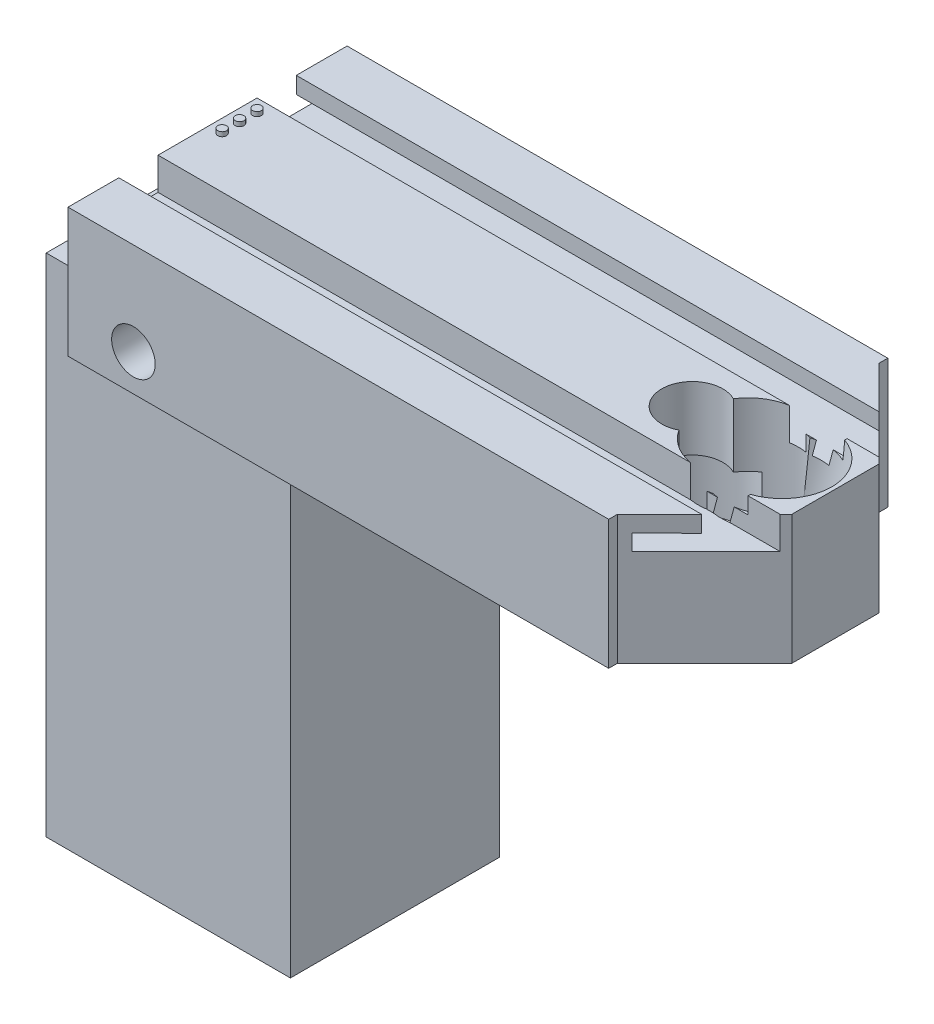
SolidWorks part; units mm, degrees
ref_plane "Front Plane" through (0, 0, 0) normal (0, 0, 1) x (1, 0, 0)
ref_plane "Top Plane" through (0, 0, 0) normal (0, 1, 0) x (1, 0, 0)
ref_plane "Right Plane" through (0, 0, 0) normal (1, 0, 0) x (0, 0, -1)
sketch "Sketch1" plane through (0, 0, 0) normal (0, 1, 0) x (1, 0, 0)
  line L0 (0, 15) -> (0, -15) construction
  line L1 (-23.5, -15) -> (23.5, -15)
  line L2 (-23.5, -15) -> (-23.5, 15)
  line L3 (-23.5, 15) -> (23.5, 15)
  line L4 (23.5, -15) -> (23.5, 15)
  line L5 (-23.5, -15) -> (23.5, 15) construction
  line L6 (-23.5, 15) -> (23.5, -15) construction
  point P0 (0, 0)
  dimension "D1" = 30
  dimension "D2" = 47
extrude "Boss-Extrude1" add sketch "Sketch1" along normal blind 14.8
sketch "Sketch2" plane through (0, 0, 0) normal (0, -1, 0) x (1, 0, 0)
  line L0 (16, 10) -> (16, -10) construction
  line L1 (7.75, 0) -> (20.75, 0) construction
  line L3 (23.5, 15) -> (23.5, -15) construction
  circle A0 centre (13.5, 0) radius 5.75
  point P13 (23.5, 0)
  dimension "D1" = 11.5
  dimension "D2" = 10
  dimension "D4" = 8.25
  dimension "D5" = 7.5
extrude "Cut-Extrude1" cut sketch "Sketch2" against normal through all
sketch "Sketch10" plane through (0, 0, 15) normal (0, 0, 1) x (1, 0, 0)
  line L1 (-23.5, 0) -> (-8.5, 0)
  line L2 (-23.5, 0) -> (-23.5, 23)
  line L3 (-23.5, 23) -> (-8.5, 23)
  line L4 (-8.5, 0) -> (-8.5, 23)
  line L6 (-23.5, 0) -> (23.5, 0) construction
  line L7 (-23.5, 14.8) -> (-23.5, 0) construction
  dimension "D1" = 23
  dimension "D2" = 15
  dimension "D3" = 0
extrude "Boss-Extrude2" add sketch "Sketch10" along normal blind 10
sketch "Sketch9" plane through (0, 0, 25) normal (0, 0, 1) x (1, 0, 0)
  line L0 (-8.5, 0) -> (-8.5, 14.8) construction
  line L2 (-20.445, 8.382) -> (-20.445, 0)
  line L3 (-20.445, 0) -> (-11.555, 0)
  line L4 (-11.555, 8.382) -> (-11.555, 0)
  line L5 (-11.555, 0) -> (-8.5, 0)
  line L7 (-20.445, 8.382) -> (-11.555, 8.382)
  line L9 (-23.5, 0) -> (-20.445, 0) construction
  circle A0 centre (-16, 4.191) radius 2.5
  point P0 (-16, 8.382)
  point P11 (-20.445, 4.191)
  line M21 (-23.5, 0) -> (-8.5, 0)
  dimension "D3" = 5
  dimension "D1" = 8.89
  dimension "D2" = 8.382
  dimension "D4" = 3.055
extrude "Cut-Extrude2" cut sketch "Sketch9" against normal through all contours A0 region at (-16, 4.191, 25)
extrude "Cut-Extrude3" cut sketch "Sketch9<3>" against normal blind 28.04 contours L7 L2 L4 A0 M21 region at (-16, 8.2598, 25)
sketch "Sketch9<3>" plane through (0, 0, 25) normal (0, 0, 1) x (1, 0, 0) same geometry as "Sketch9"
sketch "Sketch14" plane through (0, 0, 15) normal (0, 0, 1) x (1, 0, 0)
  line L0 (-8.5, 0) -> (23.5, 0) construction
  line L1 (-22.9046, 9.4802) -> (-11.7517, 9.4802)
  line L2 (-22.9046, 9.4802) -> (-22.9046, 0)
  line L3 (-22.9046, 0) -> (-11.7517, 0)
  line L4 (-11.7517, 9.4802) -> (-11.7517, 0)
extrude "Boss-Extrude3" add sketch "Sketch14" against normal blind 11.96
sketch "Sketch15" plane through (0, 0, -15) normal (0, 0, -1) x (-1, 0, 0)
  circle A0 centre (16, 4.191) radius 2.5
extrude "Cut-Extrude6" cut sketch "Sketch15" against normal blind 111 and the other way blind 31
chamfer "Chamfer1" distance 10 angle 45 2 edges at (23.5, 7.4, -15) (23.5, 7.4, 15)
sketch "Sketch16" plane through (-23.5, 0, 0) normal (-1, 0, 0) x (0, 0, 1)
  line L0 (0, 14.8) -> (0, 0) construction
  line L1 (-15, 14.8) -> (15, 14.8) construction
  line L2 (15, 0) -> (15, 14.8) construction
  line L3 (10.175, 14.8) -> (10.175, 12.9)
  line L4 (10.175, 12.9) -> (14.1747, 12.9515)
  line L5 (14.175, 11.1015) -> (5.675, 11.1)
  line L6 (14.175, 11.1015) -> (14.1747, 12.9515)
  line L7 (5.675, 11.1) -> (5.675, 14.8)
  line L8 (5.675, 14.8) -> (10.175, 14.8)
  line L9 (-14.175, 11.1015) -> (-5.675, 11.1)
  line L10 (-5.675, 11.1) -> (-5.675, 14.8)
  line L11 (-5.675, 14.8) -> (-10.175, 14.8)
  line L12 (-10.175, 14.8) -> (-10.175, 12.9)
  line L13 (-10.175, 12.9) -> (-14.1747, 12.9515)
  line L14 (-14.175, 11.1015) -> (-14.1747, 12.9515)
  dimension "D1" = 4.825
  dimension "D2" = 4.5
  dimension "D3" = 3.7
  dimension "D4" = 1.9
  dimension "D5" = 4
  dimension "D6" = 8.5
  dimension "D7" = 90
  dimension "D8" = 1.85
extrude "Cut-Extrude7" cut sketch "Sketch16" against normal through all
sketch "Sketch17" plane through (0, 0, 25) normal (0, 0, 1) x (1, 0, 0)
  line L1 (-23.5, 23) -> (-8.5, 23)
  line L2 (-23.5, 23) -> (-23.5, 0)
  line L3 (-23.5, 0) -> (-8.5, 0)
  line L4 (-8.5, 23) -> (-8.5, 0)
extrude "Cut-Extrude8" cut sketch "Sketch17" against normal up to surface (10 mm away) up to face at (2.5, 7.4, 15)
ref_plane "Plane1" through (2.1258, 7.9336, 0) normal (0.2588, 0.9659, 0) x (0, 0, 1)
sketch "Sketch18" plane through (2.1258, 7.9336, 0) normal (0.2588, 0.9659, 0) x (0, 0, 1)
  line L0 (5, 22.6993) -> (-5, 22.6993) construction
  circle A0 centre (0, 12.6993) radius 5.75
  dimension "D1" = 10
extrude "Cut-Extrude9" cut sketch "Sketch18" against normal through all and the other way through all
sketch "Sketch19" plane through (0, 14.8, 0) normal (0, 1, 0) x (1, 0, 0)
  line L0 (10.2824, 4.7757) -> (10.2824, -4.7757) construction
  circle A0 centre (7.08, 0) radius 5.75
  arc A1 (12.5743, 5.675) -> (12.5743, -5.675) centre (13.5, 0) ccw construction
  circle A2 centre (7.08, 0) radius 3.5
  dimension "D1" = 11.5
  dimension "D4" = 7
  dimension "D2" = 9.5513
  dimension "D3" = 6.42
extrude "Cut-Extrude10" cut sketch "Sketch19" against normal through all from offset 7.3 contours A0 offset against normal yes
sketch "Sketch20" plane through (0, 0, 15) normal (0, 0, 1) x (1, 0, 0)
  line L1 (-23.5, 0) -> (13.5, 0)
  line L2 (-23.5, 0) -> (-23.5, 14.8)
  line L3 (-23.5, 14.8) -> (13.5, 14.8)
  line L4 (13.5, 0) -> (13.5, 14.8)
  circle A0 centre (-16, 4.191) radius 2.5
extrude "Boss-Extrude4" add sketch "Sketch20" along normal blind 1
sketch "Sketch21" plane through (0, 0, -15) normal (0, 0, -1) x (-1, 0, 0)
  line L1 (23.5, 0) -> (-13.5, 0)
  line L2 (23.5, 0) -> (23.5, 14.8)
  line L3 (23.5, 14.8) -> (-13.5, 14.8)
  line L4 (-13.5, 0) -> (-13.5, 14.8)
  circle A0 centre (16, 4.191) radius 2.5
extrude "Boss-Extrude5" add sketch "Sketch21" along normal blind 1
sketch "Sketch23" plane through (-23.5, 0, 0) normal (-1, 0, 0) x (0, 0, 1)
  line L0 (-10.175, 14.8) -> (-16, 14.8)
  line L1 (-16, 14.8) -> (-16, 0)
  line L2 (-16, 0) -> (16, 0)
  line L3 (16, 0) -> (16, 14.8)
  line L4 (16, 14.8) -> (10.175, 14.8)
  line L5 (10.175, 14.8) -> (10.175, 12.9)
  line L6 (10.175, 12.9) -> (14.1747, 12.9515)
  line L7 (14.1747, 12.9515) -> (14.175, 11.1015)
  line L8 (14.175, 11.1015) -> (5.675, 11.1)
  line L9 (5.675, 11.1) -> (5.675, 14.8)
  line L10 (5.675, 14.8) -> (-5.675, 14.8)
  line L11 (-5.675, 14.8) -> (-5.675, 11.1)
  line L12 (-5.675, 11.1) -> (-14.175, 11.1015)
  line L13 (-14.175, 11.1015) -> (-14.1747, 12.9515)
  line L14 (-14.1747, 12.9515) -> (-10.175, 12.9)
  line L15 (-10.175, 12.9) -> (-10.175, 14.8)
extrude "Boss-Extrude6" add sketch "Sketch23" along normal blind 25
sketch "Sketch22" plane through (0, 0, 10.175) normal (0, 0, -1) x (-1, 0, 0)
  line L0 (-18.325, 12.9) -> (48.5, 12.9) construction
  line L1 (-19.1594, 14.8) -> (-14.0436, 14.8)
  line L2 (-19.1594, 14.8) -> (-19.1594, 12.9)
  line L3 (-19.1594, 12.9) -> (-14.0436, 12.9)
  line L4 (-14.0436, 14.8) -> (-14.0436, 12.9)
  line L5 (-18.325, 14.8) -> (48.5, 14.8) construction
extrude "Cut-Extrude11" cut sketch "Sketch22" along normal up to surface (20.35 mm away) up to face at (-15.0875, 13.85, -10.175)
sketch "Sketch24" plane through (0, 0, 16) normal (0, 0, 1) x (1, 0, 0)
  line L0 (-16, 4.191) -> (-41, 4.191) construction
  circle A0 centre (-41, 4.191) radius 2.5
  dimension "D1" = 25
extrude "Cut-Extrude12" cut sketch "Sketch24" against normal through all
sketch "Sketch25" plane through (0, 0, 16) normal (0, 0, 1) x (1, 0, 0)
  line L1 (-45.7, -0.259) -> (-36.3, -0.259)
  line L2 (-45.7, -0.259) -> (-45.7, 8.641)
  line L3 (-45.7, 8.641) -> (-36.3, 8.641)
  line L4 (-36.3, -0.259) -> (-36.3, 8.641)
  line L5 (-45.7, -0.259) -> (-36.3, 8.641) construction
  line L6 (-45.7, 8.641) -> (-36.3, -0.259) construction
  point P0 (-41, 4.191)
  dimension "D1" = 9.4
  dimension "D2" = 8.9
extrude "Cut-Extrude13" cut sketch "Sketch25" along normal up to surface (6.08 mm away) from surface up to face at (-13.5, 4.191, 3.04) starting at face at (-13.5, 4.191, -3.04)
sketch "Sketch26" plane through (0, 0, 16) normal (0, 0, 1) x (1, 0, 0)
  line L0 (-48.5, 0) -> (13.5, 0) construction
  line L1 (-27.6639, 8.382) -> (-4.3361, 8.382)
  line L2 (-27.6639, 8.382) -> (-27.6639, 0)
  line L3 (-27.6639, 0) -> (-4.3361, 0)
  line L4 (-4.3361, 8.382) -> (-4.3361, 0)
  line L5 (-27.6639, 8.382) -> (-4.3361, 0) construction
  line L6 (-27.6639, 0) -> (-4.3361, 8.382) construction
  point P0 (-16, 4.191)
extrude "Boss-Extrude7" add sketch "Sketch26" against normal through all
sketch "Sketch27" plane through (0, 7.5, 0) normal (0, -1, 0) x (1, 0, 0)
  line L0 (7.08, 0) -> (7.08, 5.75) construction
  arc A0 (10.29, 4.7706) -> (10.29, -4.7706) centre (7.08, 0) ccw construction
  circle A1 centre (7.08, 0) radius 3.5
extrude "Cut-Extrude14" cut sketch "Sketch27" against normal blind 10
sketch "Sketch28" plane through (0, 14.8, 0) normal (0, 1, 0) x (1, 0, 0)
  line L0 (-48.5, 5.675) -> (-47, 5.675) construction
  line L1 (12.5743, 5.675) -> (-48.5, 5.675) construction
  line L2 (-47, 5.675) -> (-47, 4.175) construction
  circle A0 centre (-47, 0.175) radius 0.5
  circle A1 centre (-47, 2.175) radius 0.5
  circle A2 centre (-47, 4.175) radius 0.5
  dimension "D1" = 3
  dimension "D2" = 1.5
  dimension "D3" = 1.5
extrude "Boss-Extrude8" add sketch "Sketch28" along normal blind 0.5
sketch "Sketch29" plane through (0, 0, 0) normal (0, -1, 0) x (1, 0, 0)
  line L0 (-45.7, 3.04) -> (-36.3, -3.04) construction
  line L2 (-50.75, -7.4) -> (-31.25, -7.4)
  line L3 (-50.75, -7.4) -> (-50.75, 7.4)
  line L4 (-50.75, 7.4) -> (-31.25, 7.4)
  line L5 (-31.25, -7.4) -> (-31.25, 7.4)
  line L6 (-50.75, -7.4) -> (-31.25, 7.4) construction
  line L7 (-50.75, 7.4) -> (-31.25, -7.4) construction
  line L8 (-55, -12) -> (-27, -12)
  line L9 (-55, -12) -> (-55, 12)
  line L10 (-55, 12) -> (-27, 12)
  line L11 (-27, -12) -> (-27, 12)
  line L12 (-55, -12) -> (-27, 12) construction
  line L13 (-55, 12) -> (-27, -12) construction
  point P4 (-41, 0)
  point P9 (-41, 0)
  dimension "D1" = 14.8
  dimension "D2" = 19.5
  dimension "D3" = 24
  dimension "D4" = 28
extrude "Boss-Extrude9" add sketch "Sketch29" along normal blind 53
sketch "Sketch30" plane through (0, 0, 0) normal (0, 1, 0) x (1, 0, 0)
  line L1 (-55, 12) -> (-48.5, 12)
  line L2 (-55, 12) -> (-55, -12)
  line L3 (-55, -12) -> (-48.5, -12)
  line L4 (-48.5, 12) -> (-48.5, -12)
extrude "Boss-Extrude10" add sketch "Sketch30" along normal blind 5
